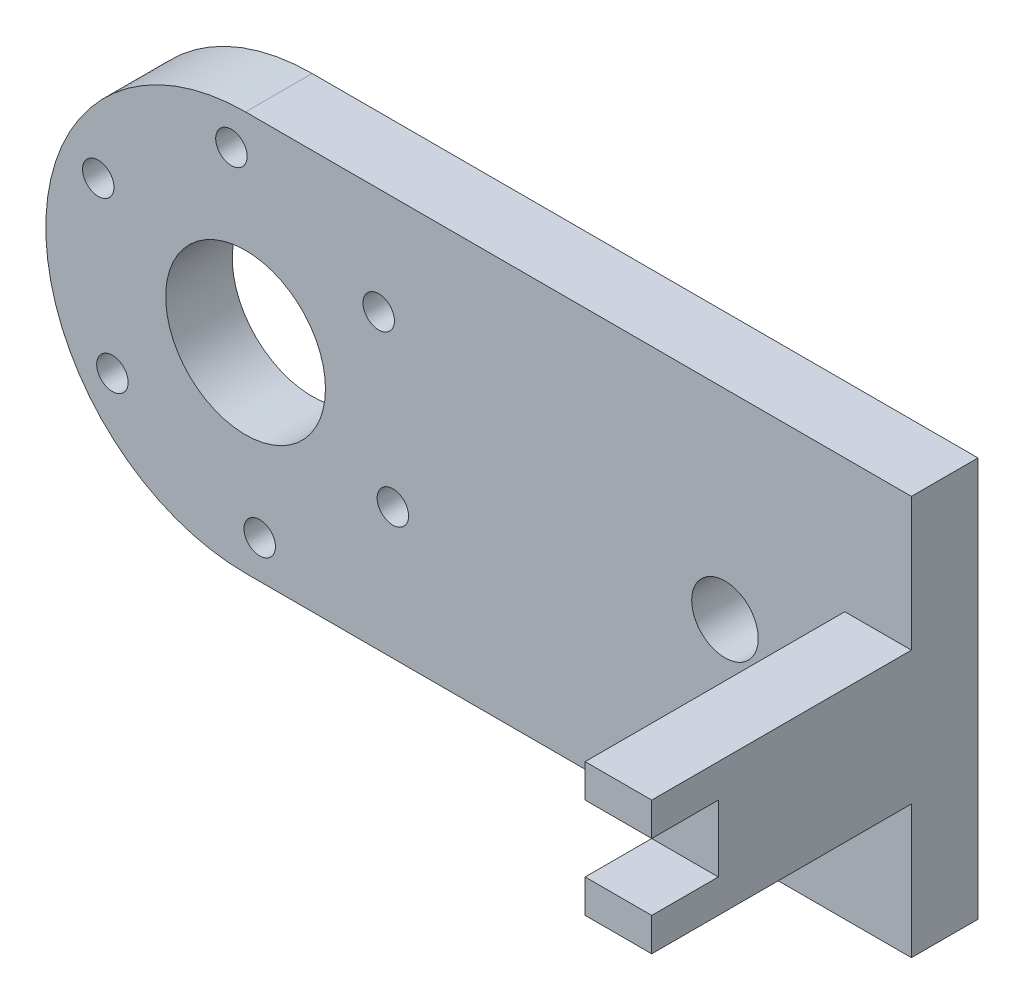
SolidWorks part; units mm, degrees
ref_plane "Front Plane" through (0, 0, 0) normal (0, 0, 1) x (1, 0, 0)
ref_plane "Top Plane" through (0, 0, 0) normal (0, 1, 0) x (1, 0, 0)
ref_plane "Right Plane" through (0, 0, 0) normal (1, 0, 0) x (0, 0, -1)
sketch "Sketch1" plane through (0, 0, 0) normal (0, 0, 1) x (1, 0, 0)
  line L1 (0, 19.05) -> (63.5, 19.05)
  line L2 (0, 19.05) -> (0, -19.05)
  line L3 (0, -19.05) -> (63.5, -19.05)
  line L4 (63.5, 19.05) -> (63.5, -19.05)
  circle A0 centre (0, 0) radius 19.05
  point P7 (0, -19.05)
  dimension "D1" = 38.1
  dimension "D2" = 63.5
extrude "Boss-Extrude1" add sketch "Sketch1" along normal blind 6.35 contours L2 L1 L4 L3 | A0
sketch "Sketch2" plane through (0, 0, 6.35) normal (0, 0, 1) x (1, 0, 0)
  line L0 (0, 0) -> (0, 15.5) construction
  line L1 (0, 0) -> (-1.3509, 15.441) construction
  line L2 (0, 0) -> (1.3509, -15.441) construction
  circle A0 centre (0, 0) radius 7.62
  circle A1 centre (0, 0) radius 15.5 construction
  circle A2 centre (-1.3509, 15.441) radius 1.5
  circle A3 centre (12.6969, 8.8904) radius 1.5
  circle A4 centre (14.0478, -6.5506) radius 1.5
  circle A5 centre (1.3509, -15.441) radius 1.5
  circle A6 centre (-12.6969, -8.8904) radius 1.5
  circle A7 centre (-14.0478, 6.5506) radius 1.5
  point P7 (1.3551, -15.4407)
  point P8 (-4.724, 14.7626)
  point P9 (1.4115, -15.441)
  point P20 (0, 0)
  dimension "D1" = 15.24
  dimension "D2" = 31
  dimension "D4" = 3
  dimension "D3" = 5
  dimension "D5" = 6
extrude "Cut-Extrude1" cut sketch "Sketch2" against normal through all
ref_plane "Plane1" through (0, 0, 0) normal (0, 1, 0) x (1, 0, 0)
sketch "Sketch4" plane through (0, 0, 0) normal (0, 1, 0) x (1, 0, 0)
  line L1 (63.5, -6.35) -> (57.15, -6.35)
  line L2 (63.5, -6.35) -> (63.5, -31.115)
  line L3 (63.5, -31.115) -> (57.15, -31.115)
  line L4 (57.15, -6.35) -> (57.15, -31.115)
  dimension "D1" = 6.35
  dimension "D2" = 24.765
extrude "Boss-Extrude2" add sketch "Sketch4" along normal mid plane 12.7
sketch "Sketch5" plane through (63.5, 0, 0) normal (1, 0, 0) x (0, 0, -1)
  line L0 (-31.115, 6.35) -> (-31.115, -6.35) construction
  line L1 (-31.115, 3.175) -> (-24.765, 3.175)
  line L2 (-31.115, 3.175) -> (-31.115, -3.175)
  line L3 (-31.115, -3.175) -> (-24.765, -3.175)
  line L4 (-24.765, 3.175) -> (-24.765, -3.175)
  line L5 (0, 0) -> (-31.115, 0) construction
  line L6 (20.3625, 0) -> (-20.3625, 0) construction
  point P11 (-24.765, 0)
  dimension "D1" = 6.35
  dimension "D2" = 6.35
extrude "Cut-Extrude2" cut sketch "Sketch5" against normal up to next
sketch "Sketch6" plane through (0, 0, 0) normal (0, 0, -1) x (-1, 0, 0)
  line L0 (-63.5, 0) -> (0, 0) construction
  line L1 (-63.5, 19.05) -> (-63.5, -19.05) construction
  circle A0 centre (-45.72, 0) radius 3.175
  point P7 (-33.02, 0)
  dimension "D1" = 6.35
  dimension "D2" = 45.72
extrude "Cut-Extrude3" cut sketch "Sketch6" against normal up to next
